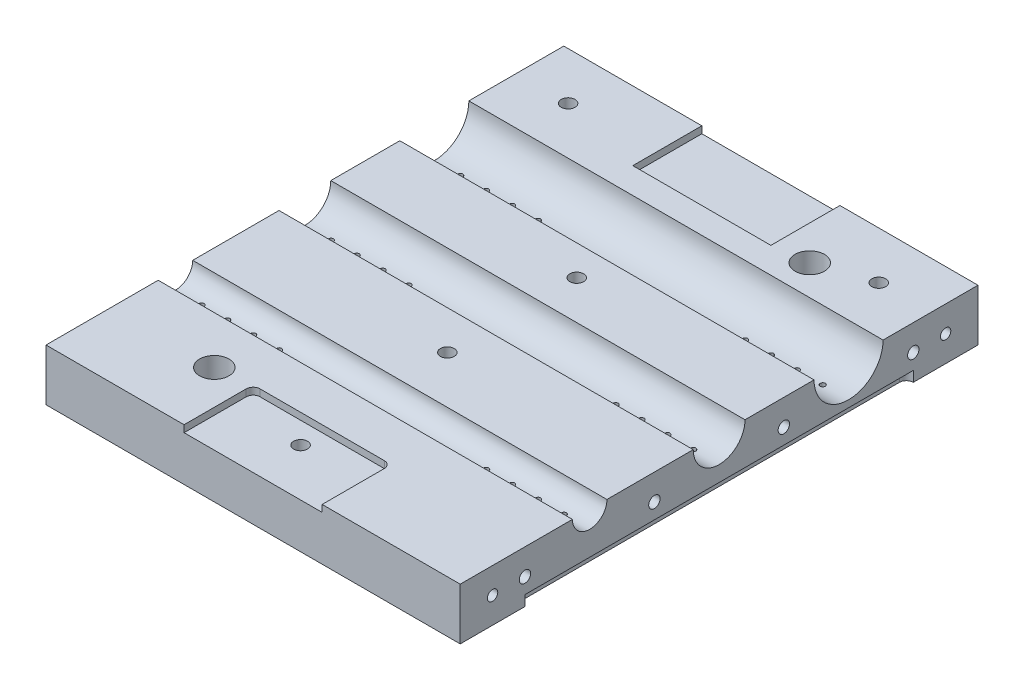
SolidWorks part; units mm, degrees
ref_plane "Front Plane" through (0, 0, 0) normal (0, 0, 1) x (1, 0, 0)
ref_plane "Top Plane" through (0, 0, 0) normal (0, 1, 0) x (1, 0, 0)
ref_plane "Right Plane" through (0, 0, 0) normal (1, 0, 0) x (0, 0, -1)
sketch "Sketch1" plane through (0, 0, 0) normal (0, 1, 0) x (1, 0, 0)
  line L1 (-44.5273, 32.3719) -> (75.4727, 32.3719)
  line L2 (-44.5273, 32.3719) -> (-44.5273, -117.6281)
  line L3 (-44.5273, -117.6281) -> (75.4727, -117.6281)
  line L4 (75.4727, 32.3719) -> (75.4727, -117.6281)
  dimension "D1" = 120
  dimension "D2" = 150
extrude "Boss-Extrude1" add sketch "Sketch1" along normal blind 15
sketch "Sketch2" plane through (75.4727, 0, 0) normal (1, 0, 0) x (0, 0, -1)
  line L0 (-42.6281, 15) -> (-42.6281, 0) construction
  line L1 (-117.6281, 15) -> (32.3719, 15) construction
  line L2 (-117.6281, 0) -> (32.3719, 0) construction
  line L3 (-117.6281, 0) -> (-42.6281, 0) construction
  line L4 (-80.1281, 0) -> (-80.1281, 15) construction
  circle A0 centre (-80.1281, 15) radius 5
  circle A1 centre (-42.6281, 15) radius 7.5
  circle A2 centre (-5.1281, 15) radius 10
  dimension "D1" = 10
  dimension "D2" = 15
  dimension "D3" = 20
extrude "Cut-Extrude1" cut sketch "Sketch2" against normal through all
sketch "Sketch3" plane through (75.4727, 0, 0) normal (1, 0, 0) x (0, 0, -1)
  line L0 (-42.6281, 0) -> (-42.6281, 15) construction
  line L1 (-103.8781, 7.5) -> (-117.6281, 7.5) construction
  line L2 (-103.8781, 15) -> (-103.8781, 0) construction
  line L3 (4.8719, 15) -> (32.3719, 15) construction
  line L4 (18.6219, 15) -> (18.6219, 0) construction
  line L5 (-117.6281, 0) -> (32.3719, 0) construction
  line L6 (18.6219, 7.5) -> (32.3719, 7.5) construction
  line L8 (32.3719, 15) -> (32.3719, 0) construction
sketch "Sketch5" plane through (0, 15, 0) normal (0, 1, 0) x (1, 0, 0)
  line L0 (75.4727, -103.8781) -> (-44.5273, -103.8781) construction
  line L1 (-44.5273, -85.1281) -> (-44.5273, -117.6281) construction
  line L2 (45.4727, 18.6219) -> (75.4727, 18.6219) construction
  line L3 (-14.5273, 18.6219) -> (-44.5273, 18.6219) construction
  line L4 (-44.5273, 32.3719) -> (-44.5273, 4.8719) construction
  line L5 (15.4727, -103.8781) -> (15.4727, 18.6219) construction
  line L6 (45.4727, 18.6219) -> (45.4727, 32.3719) construction
  line L7 (75.4727, 32.3719) -> (-44.5273, 32.3719) construction
  line L8 (-14.5273, 18.6219) -> (-14.5273, 32.3719) construction
  line L9 (-29.5273, 18.6219) -> (-29.5273, 32.3719) construction
  line L10 (75.4727, 4.8719) -> (75.4727, 32.3719) construction
  line L11 (60.4727, 18.6219) -> (60.4727, 32.3719) construction
sketch "Sketch7" plane through (0, 0, 117.6281) normal (0, 0, 1) x (1, 0, 0)
  line L0 (15.4727, 15) -> (15.4727, 0) construction
  line L1 (-44.5273, 15) -> (75.4727, 15) construction
  line L2 (-44.5273, 0) -> (75.4727, 0) construction
sketch "Sketch8" plane through (0, 15, 0) normal (0, 1, 0) x (1, 0, 0)
  line L0 (15.4727, -117.6281) -> (15.4727, -146.7177) construction
  line L1 (-44.5273, -117.6281) -> (75.4727, -117.6281) construction
ref_plane "Plane1" through (15.4727, 0, 0) normal (1, 0, 0) x (0, 0, -1)
sketch "Sketch9" plane through (0, 15, 0) normal (0, 1, 0) x (1, 0, 0)
  line L0 (35.4727, -117.6281) -> (-4.5273, -117.6281)
  line L1 (-44.5273, -117.6281) -> (75.4727, -117.6281) construction
  line L2 (-4.5273, -117.6281) -> (-4.5273, -97.6281)
  line L3 (-4.5273, -97.6281) -> (35.4727, -97.6281)
  line L5 (15.4727, -117.6281) -> (15.4727, -97.6281) construction
  line L6 (35.4727, -117.6281) -> (35.4727, -97.6281)
  dimension "D1" = 20
  dimension "D2" = 20
  dimension "D3" = 20
extrude "Cut-Extrude2" cut sketch "Sketch9" against normal blind 2 contours L3 L6 L0 L2
sketch "Sketch10" plane through (0, 15, 0) normal (0, 1, 0) x (1, 0, 0)
  line L0 (75.4727, -42.6281) -> (101.4988, -42.6281) construction
ref_plane "Plane2" through (0, 0, 42.6281) normal (0, 0, 1) x (1, 0, 0)
mirror "Mirror2" about plane through (0, 0, 42.6281) normal (0, 0, 1) of "Cut-Extrude2"
sketch "Sketch11" plane through (75.4727, 0, 0) normal (1, 0, 0) x (0, 0, -1)
  line L0 (-61.3781, 15) -> (-61.3781, 0) construction
  line L1 (-80.1281, 15) -> (-80.1281, 0) construction
  line L2 (-117.6281, 0) -> (32.3719, 0) construction
  line L3 (-80.1281, 15) -> (-42.6281, 15) construction
  line L4 (-80.1281, 7.5) -> (-61.3781, 7.5) construction
hole_wizard "M4 Tapped Hole2" positions "3DSketch4" profile "Sketch12" tap size "M4" standard "ISO"
sketch3d "3DSketch4"
  point P0 (75.4727, 7.5, 61.3781)
sketch "Sketch12" plane through (75.4727, 7.5, 61.3781) normal (0, 1, 0) x (0, 0, -1)
  line L0 (0, 0) -> (0, 20.9914)
  line L1 (0, 20.9914) -> (1.65, 20)
  line L2 (1.65, 20) -> (1.65, 0)
  line L5 (1.65, 0) -> (0, 0)
  line L10 (0, 20.9914) -> (-1.65, 20) construction
  line L11 (0, -6.35) -> (0, 107.95) construction
  dimension "Tap Drill Dia." = 3.3
  dimension "Tap Drill Depth" = 20
  dimension "Drill Angle" = 118
cosmetic thread "Hole Thread3" parameters "D1"=15, "D2"=4
mirror "Mirror3" about plane through (0, 0, 42.6281) normal (0, 0, 1) of "M4 Tapped Hole2"
mirror "Mirror4" about plane through (15.4727, 0, 0) normal (1, 0, 0) of "Mirror3"
sketch "Sketch13" plane through (75.4727, 0, 0) normal (1, 0, 0) x (0, 0, -1)
  line L0 (-98.8781, 15) -> (-98.8781, 0) construction
  line L1 (-80.1281, 15) -> (-117.6281, 15) construction
  line L2 (-117.6281, 0) -> (32.3719, 0) construction
  line L3 (-98.8781, 7.5) -> (-61.3781, 7.5) construction
hole_wizard "M4 Tapped Hole3" positions "3DSketch5" profile "Sketch15" tap size "M4" standard "ISO"
sketch3d "3DSketch5"
  point P0 (75.4727, 7.5, 98.8781)
sketch "Sketch15" plane through (75.4727, 7.5, 98.8781) normal (0, 1, 0) x (0, 0, -1)
  line L0 (0, 0) -> (0, 20.9914)
  line L1 (0, 20.9914) -> (1.65, 20)
  line L2 (1.65, 20) -> (1.65, 0)
  line L5 (1.65, 0) -> (0, 0)
  line L10 (0, 20.9914) -> (-1.65, 20) construction
  line L11 (0, -6.35) -> (0, 107.95) construction
  dimension "Tap Drill Dia." = 3.3
  dimension "Tap Drill Depth" = 20
  dimension "Drill Angle" = 118
cosmetic thread "Hole Thread4" parameters "D1"=15, "D2"=4
mirror "Mirror5" about plane through (0, 0, 42.6281) normal (0, 0, 1) of "M4 Tapped Hole3"
mirror "Mirror6" about plane through (15.4727, 0, 0) normal (1, 0, 0) of "Mirror5"
sketch "Sketch16" plane through (0, 15, 0) normal (0, 1, 0) x (1, 0, 0)
  line L0 (67.9727, -5.1281) -> (60.4727, -5.1281) construction
  line L2 (45.4727, -42.6281) -> (60.4727, -42.6281) construction
  line L3 (45.4727, -42.6281) -> (45.4727, 32.3719) construction
  line L4 (60.4727, -42.6281) -> (60.4727, 32.3719) construction
  line L5 (75.4727, 32.3719) -> (35.4727, 32.3719) construction
  line L6 (60.4727, -42.6281) -> (75.4727, -42.6281) construction
  line L7 (52.9727, -42.6281) -> (52.9727, 32.3719) construction
  line L8 (67.9727, -42.6281) -> (67.9727, 32.3719) construction
  line L10 (60.4727, -5.1281) -> (52.9727, -5.1281) construction
  line L11 (52.9727, -5.1281) -> (45.4727, -5.1281) construction
hole_wizard "Ø1.5mm Dowel Hole1" positions "3DSketch8" profile "Sketch19" hole size "Ø1.5" standard "ISO"
sketch3d "3DSketch8"
  point P0 (67.9727, 15, 5.1281)
  point P3 (60.4727, 15, 5.1281)
  point P6 (52.9727, 15, 5.1281)
  point P9 (45.4727, 15, 5.1281)
  point P12 (67.9727, 15, 42.6281)
  point P15 (60.4727, 15, 42.6281)
  point P18 (52.9727, 15, 42.6281)
  point P21 (45.4727, 15, 42.6281)
sketch "Sketch19" plane through (67.9727, 15, 5.1281) normal (1, 0, 0) x (0, 0, 1)
  line L0 (0, 0) -> (0, 25.4506)
  line L1 (0, 25.4506) -> (0.75, 25)
  line L2 (0.75, 25) -> (0.75, 0)
  line L5 (0.75, 0) -> (0, 0)
  line L10 (0, 25.4506) -> (-0.75, 25) construction
  line L11 (0, -6.35) -> (0, 107.95) construction
  dimension "Hole Dia." = 1.5
  dimension "Hole Depth" = 25
  dimension "Drill Angle" = 118
mirror "Mirror7" about plane through (0, 0, 42.6281) normal (0, 0, 1) of "Ø1.5mm Dowel Hole1"
mirror "Mirror8" about plane through (15.4727, 0, 0) normal (1, 0, 0) of "Mirror7"
sketch "Sketch20" plane through (0, 0, 0) normal (0, -1, 0) x (1, 0, 0)
  line L0 (-44.5273, 5.1281) -> (-44.5273, -32.3719) construction
  line L2 (-44.5273, 5.1281) -> (-2.3322, 5.1281) construction
  line L3 (-44.5273, -13.6219) -> (-26.2678, -13.6219) construction
  line L4 (-44.5273, 80.1281) -> (-44.5273, 117.6281) construction
  line L6 (-44.5273, 80.1281) -> (5.5325, 80.1281) construction
  line L7 (-44.5273, 98.8781) -> (5.5325, 98.8781) construction
  line L8 (-44.5273, 98.8781) -> (-44.5273, -13.6219)
  line L9 (-44.5273, -13.6219) -> (-42.5273, -13.6219)
  line L10 (-42.5273, -13.6219) -> (-42.5273, 98.8781)
  line L11 (-42.5273, 98.8781) -> (-44.5273, 98.8781)
  dimension "D1" = 2
extrude "Cut-Extrude3" cut sketch "Sketch20" against normal blind 3 contours L10 L11 L8 L9
mirror "Mirror9" about plane through (15.4727, 0, 0) normal (1, 0, 0) of "Cut-Extrude3"
sketch "Sketch22" plane through (75.4727, 0, 0) normal (1, 0, 0) x (0, 0, -1)
  line L0 (-98.8781, 7.5) -> (-117.6281, 7.5) construction
  line L1 (-117.6281, 15) -> (-117.6281, 0) construction
  line L2 (-108.2531, 7.5) -> (-108.2531, 0.5) construction
  line L3 (31.8719, 0.5) -> (-117.1281, 0.5) construction
hole_wizard "Ø3.0mm Dowel Hole1" positions "3DSketch10" profile "Sketch23" hole size "Ø3.0" standard "ISO"
sketch3d "3DSketch10"
  point P0 (75.4727, 7.5, 108.2531)
sketch "Sketch23" plane through (75.4727, 7.5, 108.2531) normal (0, 1, 0) x (0, 0, -1)
  line L0 (0, 0) -> (0, 25.9013)
  line L1 (0, 25.9013) -> (1.5, 25)
  line L2 (1.5, 25) -> (1.5, 0)
  line L5 (1.5, 0) -> (0, 0)
  line L10 (0, 25.9013) -> (-1.5, 25) construction
  line L11 (0, -6.35) -> (0, 107.95) construction
  dimension "Hole Dia." = 3
  dimension "Hole Depth" = 25
  dimension "Drill Angle" = 118
mirror "Mirror10" about plane through (0, 0, 42.6281) normal (0, 0, 1) of "Ø3.0mm Dowel Hole1"
mirror "Mirror11" about plane through (15.4727, 0, 0) normal (1, 0, 0) of "Mirror10"
sketch "Sketch24" plane through (0, 0, 117.6281) normal (0, 0, 1) x (1, 0, 0)
  line L0 (35.4727, 15) -> (37.4727, 15) construction
  line L1 (35.4727, 15) -> (75.4727, 15) construction
  line L2 (35.4727, 13) -> (35.4727, 15)
  line L3 (35.4727, 15) -> (37.4727, 15)
  arc A0 (35.4727, 13) -> (37.4727, 15) centre (35.4727, 15) ccw
  dimension "D1" = 2
sketch "Sketch26" plane through (0, 0, 0) normal (0, -1, 0) x (1, 0, 0)
  line L9 (-14.5273, 98.8781) -> (19.641, 98.8781) construction
  line L10 (-14.5273, 61.3781) -> (7.0526, 61.3781) construction
  line L12 (15.4727, 23.8781) -> (45.4727, 23.8781) construction
  line L15 (45.4727, -13.6219) -> (75.4727, -13.6219) construction
hole_wizard "M10 Tapped Hole2" positions "3DSketch14" profile "Sketch30" tap size "M10" standard "ISO"
sketch3d "3DSketch14"
  point P0 (45.4727, 0, -13.6219)
  point P3 (-14.5273, 0, 98.8781)
sketch "Sketch30" plane through (45.4727, 0, -13.6219) normal (1, 0, 0) x (0, 0, -1)
  line L0 (0, 0) -> (0, 27.0537)
  line L1 (0, 27.0537) -> (4.25, 24.5)
  line L2 (4.25, 24.5) -> (4.25, 0)
  line L5 (4.25, 0) -> (0, 0)
  line L10 (0, 27.0537) -> (-4.25, 24.5) construction
  line L11 (0, -6.35) -> (0, 107.95) construction
  dimension "Tap Drill Dia." = 8.5
  dimension "Tap Drill Depth" = 24.5
  dimension "Drill Angle" = 118
cosmetic thread "Hole Thread9" parameters "D1"=15, "D2"=10
cosmetic thread "Hole Thread10" parameters "D1"=15, "D2"=10
hole_wizard "Ø4.0mm Dowel Hole1" positions "3DSketch15" profile "Sketch31" hole size "Ø4.0" standard "ISO"
sketch3d "3DSketch15"
  point P0 (60.4727, 15, -18.6219)
  point P3 (-29.5273, 15, -18.6219)
  point P6 (15.4727, 15, 103.8781)
sketch "Sketch31" plane through (60.4727, 15, -18.6219) normal (1, 0, 0) x (0, 0, 1)
  line L0 (0, 0) -> (0, 26.2017)
  line L1 (0, 26.2017) -> (2, 25)
  line L2 (2, 25) -> (2, 0)
  line L5 (2, 0) -> (0, 0)
  line L10 (0, 26.2017) -> (-2, 25) construction
  line L11 (0, -6.35) -> (0, 107.95) construction
  dimension "Hole Dia." = 4
  dimension "Hole Depth" = 25
  dimension "Drill Angle" = 118
fillet "Fillet1" radius 2 2 edges at (73.4727, 1.5, -13.6219) (73.4727, 1.5, 98.8781)
fillet "Fillet2" radius 2 2 edges at (35.4727, 14, 97.6281) (-4.5273, 14, 97.6281)
sketch "Sketch32" plane through (0, 0, 0) normal (0, -1, 0) x (-1, 0, 0)
  line L0 (-45.4727, -5.1281) -> (-45.4727, -42.6281) construction
  line L1 (-45.4727, -23.8781) -> (-15.4727, -23.8781) construction
  line L2 (-15.4727, 32.3719) -> (-15.4727, -117.6281) construction
  line L3 (-75.4727, 32.3719) -> (44.5273, 32.3719) construction
  line L4 (44.5273, -117.6281) -> (-75.4727, -117.6281) construction
  line L5 (-45.4727, -42.6281) -> (-45.4727, -80.1281) construction
  line L6 (-45.4727, -61.3781) -> (-15.4727, -61.3781) construction
hole_wizard "Ø4.0mm Dowel Hole2" positions "Sketch34" profile "Sketch33" hole size "Ø4.0" standard "ISO"
sketch "Sketch34" plane through (0, 0, 0) normal (0, -1, 0) x (-1, 0, 0)
  point P0 (-15.4727, -61.3781)
  point P3 (-15.4727, -23.8781)
sketch "Sketch33" plane through (15.4727, 0, 61.3781) normal (1, 0, 0) x (0, 0, -1)
  line L0 (0, 0) -> (0, 21.2017)
  line L1 (0, 21.2017) -> (2, 20)
  line L2 (2, 20) -> (2, 0)
  line L5 (2, 0) -> (0, 0)
  line L10 (0, 21.2017) -> (-2, 20) construction
  line L11 (0, -6.35) -> (0, 107.95) construction
  dimension "Hole Dia." = 4
  dimension "Hole Depth" = 20
  dimension "Drill Angle" = 118
